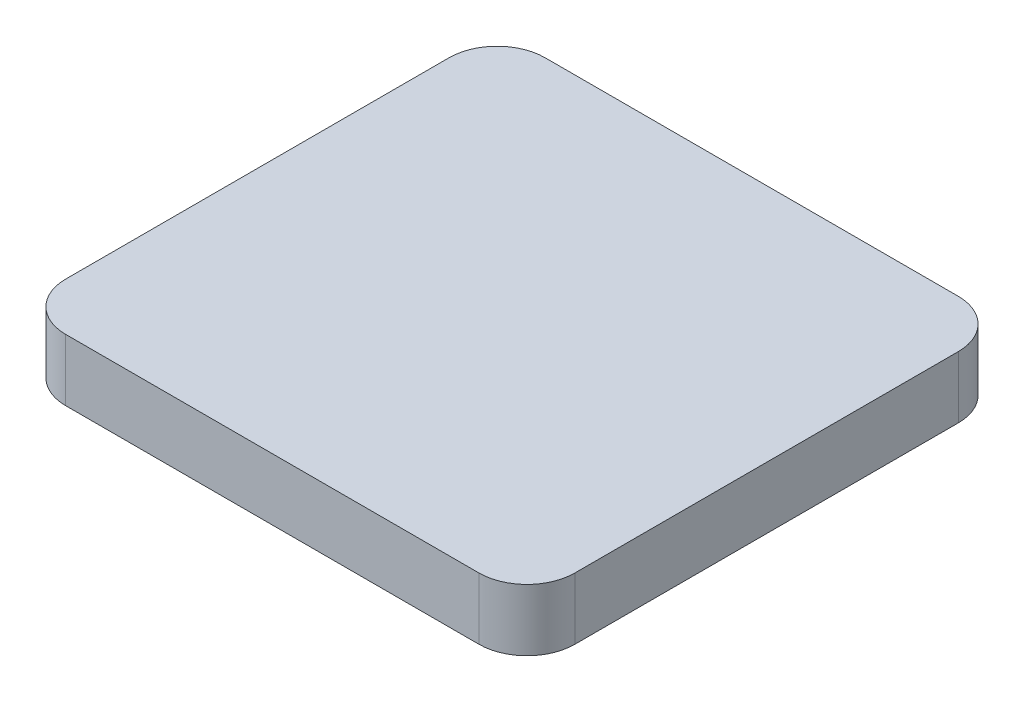
SolidWorks part; units mm, degrees
ref_plane "Front Plane" through (0, 0, 0) normal (0, 0, 1) x (1, 0, 0)
ref_plane "Top Plane" through (0, 0, 0) normal (0, 1, 0) x (1, 0, 0)
ref_plane "Right Plane" through (0, 0, 0) normal (1, 0, 0) x (0, 0, -1)
sketch "Sketch1" plane through (0, 0, 0) normal (0, 1, 0) x (1, 0, 0)
  line L0 (-21.9, 20.5) -> (-21.9, 22.5) construction
  line L1 (19.4, 20.5) -> (-19.4, 20.5)
  line L2 (21.9, 18) -> (21.9, -18)
  line L3 (19.4, -20.5) -> (-19.4, -20.5)
  line L4 (-21.9, 18) -> (-21.9, -18)
  line L5 (21.9, 20.5) -> (-21.9, -20.5) construction
  line L6 (21.9, -20.5) -> (-21.9, 20.5) construction
  line L7 (23.9, -22.5) -> (-23.9, -22.5)
  line L8 (23.9, -22.5) -> (23.9, 22.5)
  line L9 (23.9, 22.5) -> (-23.9, 22.5)
  line L10 (-23.9, -22.5) -> (-23.9, 22.5)
  line L11 (23.9, -22.5) -> (-23.9, 22.5) construction
  line L12 (23.9, 22.5) -> (-23.9, -22.5) construction
  line L13 (-21.9, 20.5) -> (-23.9, 20.5) construction
  arc A0 (-19.4, -20.5) -> (-21.9, -18) centre (-19.4, -18) cw
  arc A1 (21.9, -18) -> (19.4, -20.5) centre (19.4, -18) cw
  arc A2 (19.4, 20.5) -> (21.9, 18) centre (19.4, 18) cw
  arc A3 (-19.4, 20.5) -> (-21.9, 18) centre (-19.4, 18) ccw
  circle A4 centre (-19.4, 18) radius 4.5
  circle A5 centre (19.4, 18) radius 4.5
  circle A6 centre (19.4, -18) radius 4.5
  circle A7 centre (-19.4, -18) radius 4.5
  point P0 (0, 0)
  point P6 (0, 0)
  dimension "D4" = 2.5
  dimension "D1" = 43.8
  dimension "D2" = 41
  dimension "D3" = 2
extrude "Boss-Extrude1" add sketch "Sketch1" along normal blind 1.3 contours L1 A4 L4 A3 | A7 L4 A4 L10 | A7 L3 A0 L4 | A7 L7 A6 L3 | A6 L2 A1 L3 | A6 L8 A5 L2 | L2 A5 L1 A2 | A5 L9 A4 L1 region at (17.5292, 0, -20.6166) region at (0, 0, -21.5286) region at (-17.5292, 0, -20.6166) region at (22.9312, 0, 0) region at (23.2658, 0, 15.9336) region at (-22.9312, 0, 0) region at (0, 0, 21.5286) region at (-22.0166, 0, 16.1292)
sketch "Sketch2" plane through (0, 1.3, 0) normal (0, 1, 0) x (1, 0, 0)
  line L4 (-19.4, -22.5) -> (19.4, -22.5)
  line L5 (23.9, -18) -> (23.9, 18)
  line L6 (19.4, 22.5) -> (-19.4, 22.5)
  line L7 (-23.9, 18) -> (-23.9, -18)
  line L8 (-19.4, -22.5) -> (19.4, -22.5)
  line L9 (23.9, -18) -> (23.9, 18)
  line L10 (19.4, 22.5) -> (-19.4, 22.5)
  line L11 (-23.9, 18) -> (-23.9, -18)
  arc A4 (19.4, -22.5) -> (23.9, -18) centre (19.4, -18) ccw
  arc A5 (23.9, 18) -> (19.4, 22.5) centre (19.4, 18) ccw
  arc A6 (-19.4, 22.5) -> (-23.9, 18) centre (-19.4, 18) ccw
  arc A7 (-23.9, -18) -> (-19.4, -22.5) centre (-19.4, -18) ccw
  arc A8 (19.4, -22.5) -> (23.9, -18) centre (19.4, -18) ccw
  arc A9 (23.9, 18) -> (19.4, 22.5) centre (19.4, 18) ccw
  arc A10 (-19.4, 22.5) -> (-23.9, 18) centre (-19.4, 18) ccw
  arc A11 (-23.9, -18) -> (-19.4, -22.5) centre (-19.4, -18) ccw
  dimension "D1" = 0
extrude "Boss-Extrude2" add sketch "Sketch2" along normal blind 1.5
sketch "Sketch3" plane through (0, 1.3, 0) normal (0, -1, 0) x (1, 0, 0)
  line L0 (-23.9, 0) -> (23.9, 0) construction
  line L1 (-23.9, 18) -> (-23.9, -18) construction
  line L2 (23.9, 18) -> (23.9, -18) construction
  line L3 (-23.9, 11.25) -> (23.9, 11.25) construction
  line L4 (0, 11.25) -> (0, 22.5) construction
  line L5 (19.4, 22.5) -> (-19.4, 22.5) construction
  line L6 (0, 11.25) -> (0, 0) construction
  line L7 (-23.9, -11.25) -> (23.9, -11.25) construction
  line L8 (0, 0) -> (4.1348, 4.1348) construction
  line L9 (11.25, -23.9) -> (11.25, 23.9) construction
  line L10 (-11.25, -23.9) -> (-11.25, 23.9) construction
  line L11 (-21.9, -18) -> (-21.9, 18) construction
  line L12 (-21.9, -18) -> (-21.9, 18) construction
  line L13 (19.4, -20.5) -> (-19.4, -20.5) construction
  line L14 (21.9, -18) -> (21.9, 18) construction
  line L15 (19.4, 20.5) -> (-19.4, 20.5) construction
  line L16 (19.4, 20.5) -> (-19.4, 20.5) construction
  circle A0 centre (-21.9, 11.25) radius 0.4
  circle A1 centre (-21.9, 0) radius 0.4
  circle A2 centre (-21.9, -11.25) radius 0.4
  circle A3 centre (-11.25, -20.5) radius 0.4
  circle A4 centre (11.25, -20.5) radius 0.4
  circle A5 centre (21.9, -11.25) radius 0.4
  circle A6 centre (21.9, 0) radius 0.4
  circle A7 centre (21.9, 11.25) radius 0.4
  circle A8 centre (11.25, 20.5) radius 0.4
  circle A9 centre (0, 20.5) radius 0.4
  circle A10 centre (-11.25, 20.5) radius 0.4
  point P56 (-21.6, 0)
  point P57 (21.6, -10.85)
  dimension "D2" = 0.8
  dimension "D1" = 45
extrude "Boss-Extrude3" add sketch "Sketch3" along normal up to surface (1.3 mm away) up to face at (0, 0, 0)
sketch "Sketch4" plane through (0, 0, 0) normal (0, -1, 0) x (1, 0, 0)
  line L0 (-22.9, 18) -> (-22.9, -18)
  line L1 (-19.4, -21.5) -> (19.4, -21.5)
  line L2 (22.9, -18) -> (22.9, 18)
  line L3 (19.4, 21.5) -> (-19.4, 21.5)
  line L4 (19.4, 22.5) -> (-19.4, 22.5)
  line L5 (-23.9, 18) -> (-23.9, -18)
  line L6 (-19.4, -22.5) -> (19.4, -22.5)
  line L7 (23.9, -18) -> (23.9, 18)
  line L8 (19.4, 22.5) -> (-19.4, 22.5)
  line L9 (-23.9, 18) -> (-23.9, -18)
  line L10 (-19.4, -22.5) -> (19.4, -22.5)
  line L11 (23.9, -18) -> (23.9, 18)
  arc A0 (-19.4, 21.5) -> (-22.9, 18) centre (-19.4, 18) ccw
  arc A1 (-22.9, -18) -> (-19.4, -21.5) centre (-19.4, -18) ccw
  arc A2 (19.4, -21.5) -> (22.9, -18) centre (19.4, -18) ccw
  arc A3 (22.9, 18) -> (19.4, 21.5) centre (19.4, 18) ccw
  arc A4 (-19.4, 22.5) -> (-23.9, 18) centre (-19.4, 18) ccw
  arc A5 (-23.9, -18) -> (-19.4, -22.5) centre (-19.4, -18) ccw
  arc A6 (19.4, -22.5) -> (23.9, -18) centre (19.4, -18) ccw
  arc A7 (23.9, 18) -> (19.4, 22.5) centre (19.4, 18) ccw
  arc A8 (-19.4, 22.5) -> (-23.9, 18) centre (-19.4, 18) ccw
  arc A9 (-23.9, -18) -> (-19.4, -22.5) centre (-19.4, -18) ccw
  arc A10 (19.4, -22.5) -> (23.9, -18) centre (19.4, -18) ccw
  arc A11 (23.9, 18) -> (19.4, 22.5) centre (19.4, 18) ccw
  dimension "D1" = 0
  dimension "D2" = 1
extrude "Boss-Extrude4" add sketch "Sketch4" along normal blind 3
sketch "Sketch5" plane through (0, 1.3, 0) normal (0, -1, 0) x (1, 0, 0)
  line L31 (-12.2298, 19.5) -> (-19.4, 19.5)
  line L32 (-20.9, 18) -> (-20.9, 12.2298)
  line L33 (-20.9, 10.2702) -> (-20.9, 0.9798)
  line L34 (-20.9, -0.9798) -> (-20.9, -10.2702)
  line L35 (-20.9, -12.2298) -> (-20.9, -18)
  line L36 (-19.4, -19.5) -> (-12.2298, -19.5)
  line L37 (-10.2702, -19.5) -> (10.2702, -19.5)
  line L38 (12.2298, -19.5) -> (19.4, -19.5)
  line L39 (20.9, -18) -> (20.9, -12.2298)
  line L40 (20.9, -10.2702) -> (20.9, -0.9798)
  line L41 (20.9, 0.9798) -> (20.9, 10.2702)
  line L42 (20.9, 12.2298) -> (20.9, 18)
  line L43 (19.4, 19.5) -> (12.2298, 19.5)
  line L44 (10.2702, 19.5) -> (0.9798, 19.5)
  line L45 (-0.9798, 19.5) -> (-10.2702, 19.5)
  line L46 (-12.2298, 19.5) -> (-19.4, 19.5)
  line L47 (-20.9, 18) -> (-20.9, 12.2298)
  line L48 (-20.9, 10.2702) -> (-20.9, 0.9798)
  line L49 (-20.9, -0.9798) -> (-20.9, -10.2702)
  line L50 (-20.9, -12.2298) -> (-20.9, -18)
  line L51 (-19.4, -19.5) -> (-12.2298, -19.5)
  line L52 (-10.2702, -19.5) -> (10.2702, -19.5)
  line L53 (12.2298, -19.5) -> (19.4, -19.5)
  line L54 (20.9, -18) -> (20.9, -12.2298)
  line L55 (20.9, -10.2702) -> (20.9, -0.9798)
  line L56 (20.9, 0.9798) -> (20.9, 10.2702)
  line L57 (20.9, 12.2298) -> (20.9, 18)
  line L58 (19.4, 19.5) -> (12.2298, 19.5)
  line L59 (10.2702, 19.5) -> (0.9798, 19.5)
  line L60 (-0.9798, 19.5) -> (-10.2702, 19.5)
  arc A30 (-12.2298, 19.5) -> (-10.2702, 19.5) centre (-11.25, 20.5) ccw
  arc A31 (-19.4, 19.5) -> (-20.9, 18) centre (-19.4, 18) ccw
  arc A32 (-20.9, 10.2702) -> (-20.9, 12.2298) centre (-21.9, 11.25) ccw
  arc A33 (-20.9, -0.9798) -> (-20.9, 0.9798) centre (-21.9, 0) ccw
  arc A34 (-20.9, -12.2298) -> (-20.9, -10.2702) centre (-21.9, -11.25) ccw
  arc A35 (-20.9, -18) -> (-19.4, -19.5) centre (-19.4, -18) ccw
  arc A36 (-10.2702, -19.5) -> (-12.2298, -19.5) centre (-11.25, -20.5) ccw
  arc A37 (12.2298, -19.5) -> (10.2702, -19.5) centre (11.25, -20.5) ccw
  arc A38 (19.4, -19.5) -> (20.9, -18) centre (19.4, -18) ccw
  arc A39 (20.9, -10.2702) -> (20.9, -12.2298) centre (21.9, -11.25) ccw
  arc A40 (20.9, 0.9798) -> (20.9, -0.9798) centre (21.9, 0) ccw
  arc A41 (20.9, 12.2298) -> (20.9, 10.2702) centre (21.9, 11.25) ccw
  arc A42 (20.9, 18) -> (19.4, 19.5) centre (19.4, 18) ccw
  arc A43 (10.2702, 19.5) -> (12.2298, 19.5) centre (11.25, 20.5) ccw
  arc A44 (-0.9798, 19.5) -> (0.9798, 19.5) centre (0, 20.5) ccw
  arc A45 (-12.2298, 19.5) -> (-10.2702, 19.5) centre (-11.25, 20.5) ccw
  arc A46 (-19.4, 19.5) -> (-20.9, 18) centre (-19.4, 18) ccw
  arc A47 (-20.9, 10.2702) -> (-20.9, 12.2298) centre (-21.9, 11.25) ccw
  arc A48 (-20.9, -0.9798) -> (-20.9, 0.9798) centre (-21.9, 0) ccw
  arc A49 (-20.9, -12.2298) -> (-20.9, -10.2702) centre (-21.9, -11.25) ccw
  arc A50 (-20.9, -18) -> (-19.4, -19.5) centre (-19.4, -18) ccw
  arc A51 (-10.2702, -19.5) -> (-12.2298, -19.5) centre (-11.25, -20.5) ccw
  arc A52 (12.2298, -19.5) -> (10.2702, -19.5) centre (11.25, -20.5) ccw
  arc A53 (19.4, -19.5) -> (20.9, -18) centre (19.4, -18) ccw
  arc A54 (20.9, -10.2702) -> (20.9, -12.2298) centre (21.9, -11.25) ccw
  arc A55 (20.9, 0.9798) -> (20.9, -0.9798) centre (21.9, 0) ccw
  arc A56 (20.9, 12.2298) -> (20.9, 10.2702) centre (21.9, 11.25) ccw
  arc A57 (20.9, 18) -> (19.4, 19.5) centre (19.4, 18) ccw
  arc A58 (10.2702, 19.5) -> (12.2298, 19.5) centre (11.25, 20.5) ccw
  arc A59 (-0.9798, 19.5) -> (0.9798, 19.5) centre (0, 20.5) ccw
  dimension "D1" = 1
extrude "Cut-Extrude1" cut sketch "Sketch5" against normal blind 0.5
